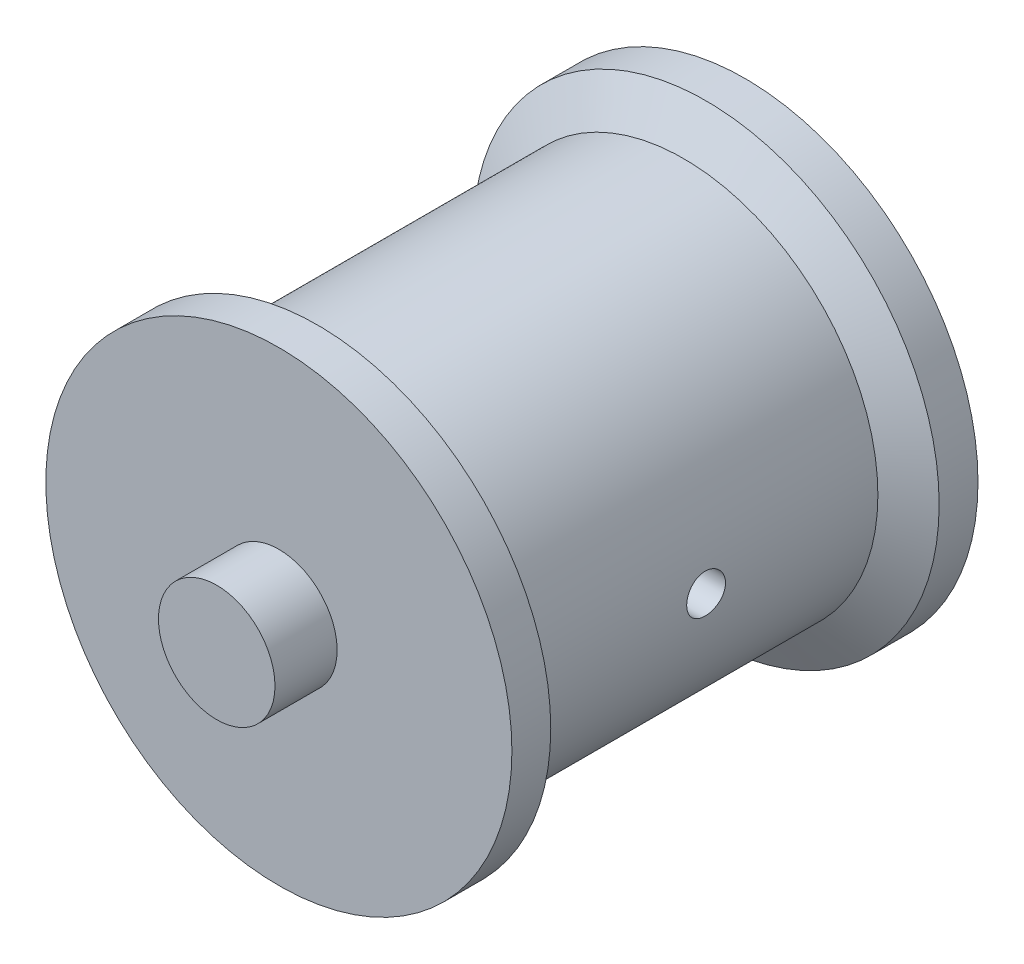
SolidWorks part; units mm, degrees
ref_plane "Front Plane" through (0, 0, 0) normal (0, 0, 1) x (1, 0, 0)
ref_plane "Top Plane" through (0, 0, 0) normal (0, 1, 0) x (1, 0, 0)
ref_plane "Right Plane" through (0, 0, 0) normal (1, 0, 0) x (0, 0, -1)
sketch "Sketch2" plane through (0, 0, 0) normal (0, 0, 1) x (1, 0, 0)
  line L0 (-1.5811, 2.25) -> (1.5811, 2.25)
  line L1 (0, 0) -> (0, -2.75) construction
  circle A0 centre (0, 0) radius 2.75
  circle A1 centre (0, 0) radius 10
  dimension "D1" = 5.5
  dimension "D2" = 20
  dimension "D3" = 5
extrude "Boss-Extrude1" add sketch "Sketch2" along normal blind 10 contours A1 A0 | L0 A0 region at (0, 2.4516, 0) region at (-9.7172, 0, 0)
sketch "Sketch3" plane through (0, 0, 10) normal (0, 0, 1) x (1, 0, 0)
  circle A0 centre (0, 0) radius 25
  dimension "D1" = 50
extrude "Boss-Extrude2" add sketch "Sketch3" along normal blind 60
sketch "Sketch4" plane through (0, 0, 70) normal (0, 0, 1) x (1, 0, 0)
  circle A0 centre (0, 0) radius 30
  circle A1 centre (0, 0) radius 25 construction
  dimension "D1" = 5
extrude "Boss-Extrude3" add sketch "Sketch4" against normal blind 5
ref_plane "Plane1" through (0, 0, 40) normal (0, 0, 1) x (1, 0, 0)
mirror "Mirror1" about plane through (0, 0, 40) normal (0, 0, 1) of "Boss-Extrude3"
chamfer "Chamfer1" distance 5 angle 30 2 edges at (25, 0, 65) (-25, 0, 15) first distance on face at (25, 0, 65) first distance on face at (-25, 0, 15)
sketch "Sketch5" plane through (0, 0, 0) normal (1, 0, 0) x (0, 0, -1)
  line L0 (-17.8868, 0) -> (-62.1132, 0) construction
  line L1 (-17.8868, -25) -> (-17.8868, 25) construction
  line L2 (-62.1132, -25) -> (-62.1132, 25) construction
  circle A0 centre (-40, 0) radius 2.5
  dimension "D1" = 5
extrude "Cut-Extrude1" cut sketch "Sketch5" against normal through all both and the other way through all
sketch "Sketch6" plane through (0, 0, 70) normal (0, 0, 1) x (1, 0, 0)
  circle A0 centre (0, 0) radius 7.5
  dimension "D1" = 15
extrude "Boss-Extrude4" add sketch "Sketch6" along normal blind 8
